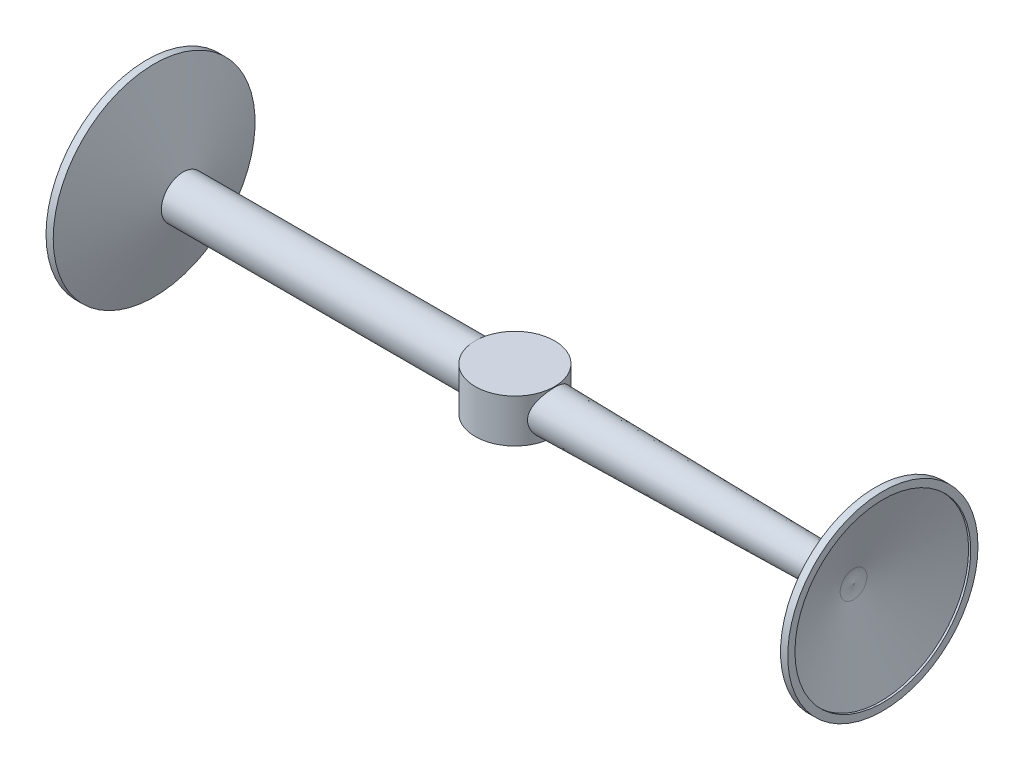
SolidWorks part; units mm, degrees
ref_plane "Front Plane" through (0, 0, 0) normal (0, 0, 1) x (1, 0, 0)
ref_plane "Top Plane" through (0, 0, 0) normal (0, 1, 0) x (1, 0, 0)
ref_plane "Right Plane" through (0, 0, 0) normal (1, 0, 0) x (0, 0, -1)
sketch "Sketch1" plane through (0, 0, 0) normal (0, 1, 0) x (1, 0, 0)
  circle A0 centre (0, 0) radius 27.5
  dimension "D1" = 55
extrude "Boss-Extrude1" add sketch "Sketch1" along normal blind 30
sketch "Sketch2" plane through (0, 0, 0) normal (0, -1, 0) x (1, 0, 0)
  circle A0 centre (0, 0) radius 25
  dimension "D1" = 50
sketch "Sketch4" plane through (0, 0, 0) normal (1, 0, 0) x (0, 0, -1)
  line L2 (-27.5, 0) -> (27.5, 0) construction
  line L3 (27.5, 0) -> (27.5, 30) construction
  circle A0 centre (0, 15) radius 15
  dimension "D1" = 15
  dimension "D2" = 30
  dimension "D3" = 27.5
extrude "Boss-Extrude3" add sketch "Sketch4" along normal blind 230 draft 1 and the other way blind 230
extrude "Cut-Extrude4" cut sketch "Sketch2" against normal blind 20
sketch "Sketch5" plane through (230, 0, 0) normal (1, 0, 0) x (0, 0, -1)
  circle A0 centre (0, 15) radius 10.9853
  dimension "D1" = 21.9707
extrude "Boss-Extrude4" add sketch "Sketch5" along normal blind 20 draft 70 draft outward yes
sketch "Sketch6" plane through (-230, 0, 0) normal (-1, 0, 0) x (0, 0, 1)
  circle A0 centre (0, 15) radius 15
extrude "Boss-Extrude5" add sketch "Sketch6" along normal blind 20 draft 70 draft outward yes
sketch "Sketch10" plane through (250, 0, 0) normal (1, 0, 0) x (0, 0, -1)
  circle A0 centre (0, 15) radius 65.9349
extrude "Boss-Extrude7" add sketch "Sketch10" along normal blind 5
sketch "Sketch11" plane through (-250, 0, 0) normal (-1, 0, 0) x (0, 0, 1)
  circle A0 centre (0, 15) radius 69.9495
extrude "Boss-Extrude8" add sketch "Sketch11" along normal blind 5
ref_plane "Plane1" through (0, 15, 0) normal (0, 1, 0) x (1, 0, 0)
sketch "Sketch12" plane through (0, 15, 0) normal (0, 1, 0) x (1, 0, 0)
  line L0 (373.2682, 0) -> (-372.8882, 0) construction
  line L13 (-234.6985, 13.2899) -> (-253.501, 64.9495)
  line L14 (-253.501, 64.9495) -> (-255, 64.9495)
  line L15 (-234.6985, 0) -> (-255, 0)
  line L16 (-255, 0) -> (-255, 64.9495)
  arc A1 (-234.6985, 13.2899) -> (-234.6985, 0) centre (-252.9553, 6.6449) cw
revolve "Cut-Revolve3" cut sketch "Sketch12" angle 360 about L0
sketch "Sketch14" plane through (0, 15, 0) normal (0, 1, 0) x (1, 0, 0)
  line L0 (84.5998, 0) -> (367.3301, 0) construction
  line L5 (255, 60.9349) -> (253.501, 60.9349)
  line L6 (253.501, 60.9349) -> (234.6985, 9.2752)
  line L7 (234.6985, 0) -> (255, 0)
  line L8 (255, 0) -> (255, 60.9349)
  arc A0 (234.6985, 9.2752) -> (234.6985, 0) centre (247.4402, 4.6376) ccw
revolve "Cut-Revolve4" cut sketch "Sketch14" angle 360 about L0
